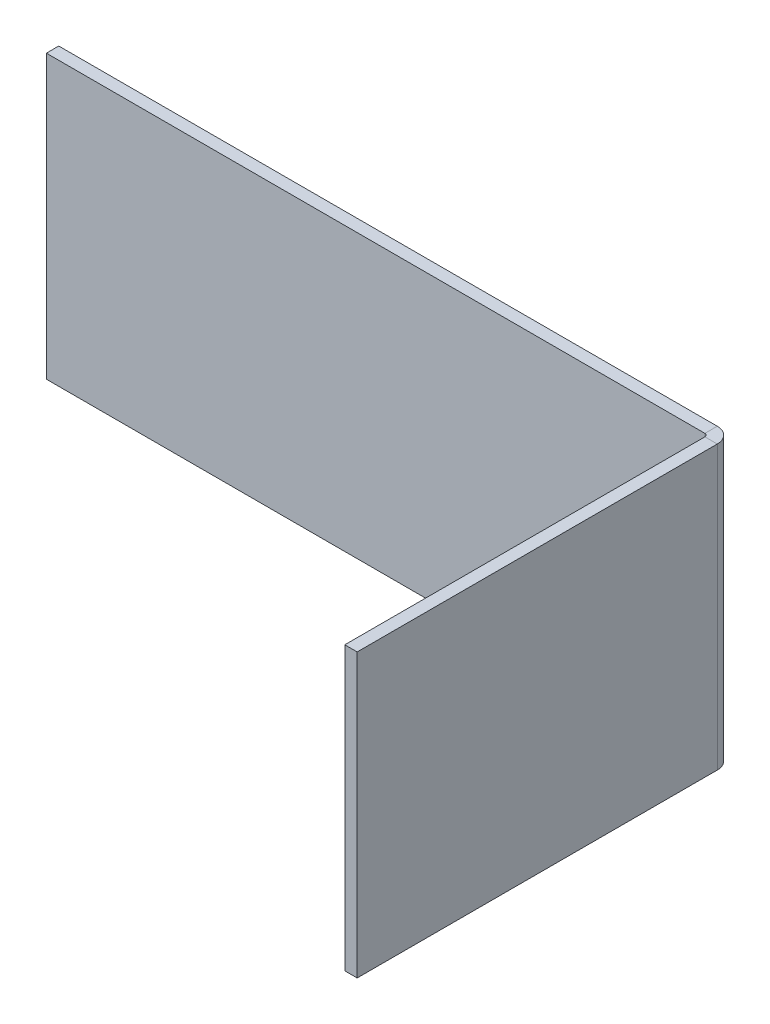
SolidWorks part; units mm, degrees
note: The reader was unsure of these and kept them because the rebuilt part matched: flange length of "Edge-Flange1".
ref_plane "Front Plane" through (0, 0, 0) normal (0, 0, 1) x (1, 0, 0)
ref_plane "Top Plane" through (0, 0, 0) normal (0, 1, 0) x (1, 0, 0)
ref_plane "Right Plane" through (0, 0, 0) normal (1, 0, 0) x (0, 0, -1)
sketch "Sketch2" plane through (0, 0, 0) normal (0, 0, 1) x (1, 0, 0)
  line L1 (-79.7873, -34.2134) -> (79.7873, -34.2134)
  line L2 (-79.7873, -34.2134) -> (-79.7873, 34.2134)
  line L3 (-79.7873, 34.2134) -> (79.7873, 34.2134)
  line L4 (79.7873, -34.2134) -> (79.7873, 34.2134)
  line L5 (-79.7873, -34.2134) -> (79.7873, 34.2134) construction
  line L6 (-79.7873, 34.2134) -> (79.7873, -34.2134) construction
  point P0 (0, 0)
base flange "Base-Flange1" sketch "Sketch2" thickness 3 reverse thickness direction no parameters "D1"=0.7366
edge flange "Edge-Flange1" sketch "Sketch9" flange angle 90 flange length 91 flange position bend outside bend radius 0.7366 thickness 3 relief rectangular parameters "D6"=10
sketch "Sketch9" plane through (79.7873, 0, 0) normal (1, 0, 0) x (0, 1, 0)
  line L2 (-34.2134, 0) -> (-34.2134, 88)
  line L3 (-34.2134, 88) -> (34.2134, 88)
  line L4 (34.2134, 88) -> (34.2134, 0)
  line L7 (-34.2134, 0) -> (34.2134, 0) construction
  line L8 (-34.2134, 0) -> (34.2134, 0)
bend "EdgeBend1" bend radius 0.7366 bend angle 90 parameters "D5"=1
sketch "Bend-Lines1" [suppressed] plane through (0, 0, 0) normal (0, 1, 0) x (1, 0, 0)
sketch "Bounding-Box1" [suppressed] plane through (0, 0, 0) normal (0, 1, 0) x (1, 0, 0)
sheet metal parameters "Sheet-Metal1" thickness 3 parameters "D1"=0.7366
flat pattern "Flat-Pattern1" [suppressed]
sketch "Bend-Lines2" plane through (0, 0, 0) normal (0, 1, 0) x (1, 0, 0)
sketch3d "Bounding-Box2" [suppressed]
  line L0 (79.7873, -34.2134, 0) -> (-79.7873, -34.2134, 0) construction
  line L1 (79.7873, 34.2134, 0) -> (-79.7873, 34.2134, 0) construction
  line L2 (79.7873, -34.2134, 0) -> (79.7873, 34.2134, 0) construction
  line L3 (-79.7873, -34.2134, 0) -> (-79.7873, 34.2134, 0) construction
sheet metal parameters "Sheet-Metal2" thickness 3 parameters "D1"=0.7366
flat pattern "Flat-Pattern1"
sketch "Bend-Lines2" plane through (0, 0, 0) normal (0, 0, 1) x (1, 0, 0)
  line L0 (81.5439, -34.2134) -> (81.5439, 34.2134) construction
  line L1 (81.5439, -34.2134) -> (81.5439, 34.2134) construction
sketch3d "Bounding-Box2" [suppressed]
  line L0 (-79.7873, -34.2134, 0) -> (170.5639, -34.2134, 0) construction
  line L1 (-79.7873, 34.2134, 0) -> (170.5639, 34.2134, 0) construction
  line L2 (-79.7873, -34.2134, 0) -> (-79.7873, 34.2134, 0) construction
  line L3 (170.5639, -34.2134, 0) -> (170.5639, 34.2134, 0) construction
bend of the flat pattern "Flatten-<EdgeBend1>1"
